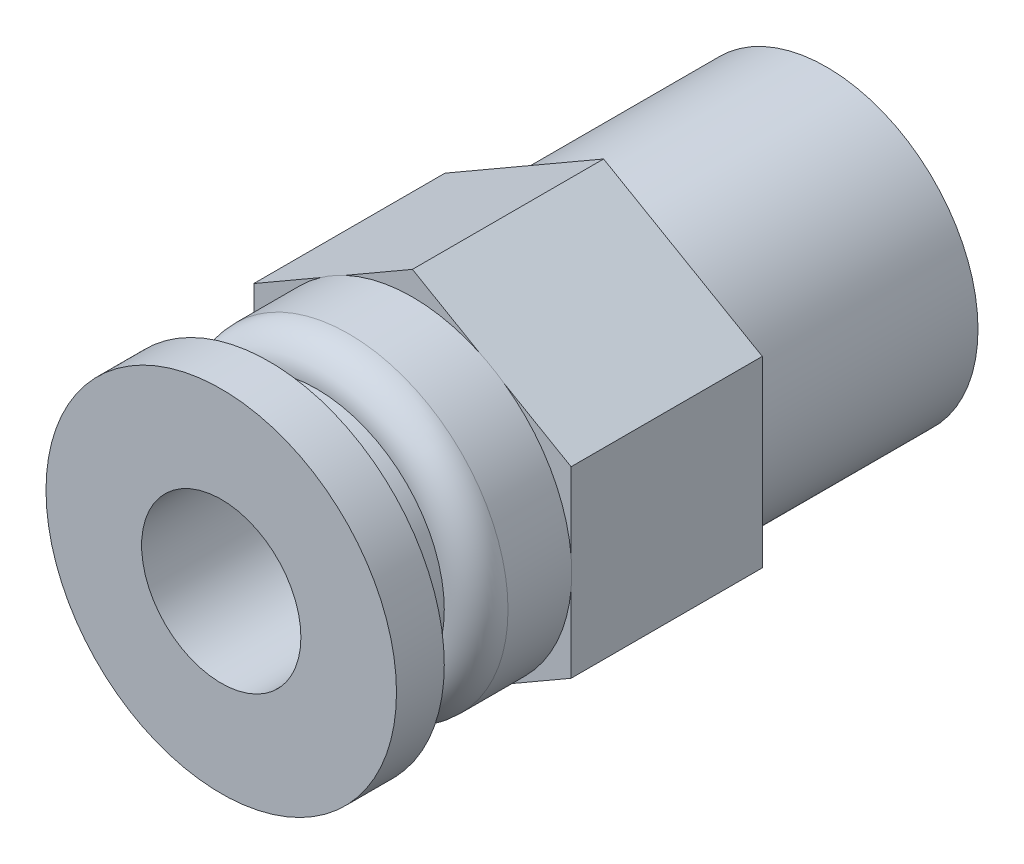
SolidWorks part; units mm, degrees
ref_plane "Front Plane" through (0, 0, 0) normal (0, 0, 1) x (1, 0, 0)
ref_plane "Top Plane" through (0, 0, 0) normal (0, 1, 0) x (1, 0, 0)
ref_plane "Right Plane" through (0, 0, 0) normal (1, 0, 0) x (0, 0, -1)
sketch "Sketch1" plane through (0, 0, 0) normal (0, 0, 1) x (1, 0, 0)
  line L1 (0, 1.5) -> (-1.299, 0.75)
  line L2 (-1.299, 0.75) -> (-1.299, -0.75)
  line L3 (-1.299, -0.75) -> (0, -1.5)
  line L4 (0, -1.5) -> (1.299, -0.75)
  line L5 (1.299, -0.75) -> (1.299, 0.75)
  line L6 (1.299, 0.75) -> (0, 1.5)
  circle A0 centre (0, 0) radius 4.75
  circle A1 centre (0, 0) radius 1.5 construction
  dimension "D1" = 9.5
  dimension "D2" = 3
extrude "Boss-Extrude1" add sketch "Sketch1" along normal blind 7
sketch "Sketch2" plane through (0, 0, 7) normal (0, 0, 1) x (1, 0, 0)
  line L1 (0, 5.75) -> (-4.9796, 2.875)
  line L2 (-4.9796, 2.875) -> (-4.9796, -2.875)
  line L3 (-4.9796, -2.875) -> (0, -5.75)
  line L4 (0, -5.75) -> (4.9796, -2.875)
  line L5 (4.9796, -2.875) -> (4.9796, 2.875)
  line L6 (4.9796, 2.875) -> (0, 5.75)
  circle A0 centre (0, 0) radius 5.75 construction
  circle A1 centre (0, 0) radius 2.5
  dimension "D1" = 11.5
  dimension "D2" = 5
extrude "Boss-Extrude2" add sketch "Sketch2" along normal blind 6
sketch "Sketch3" plane through (0, 0, 13) normal (0, 0, 1) x (1, 0, 0)
  circle A0 centre (0, 0) radius 5
  circle A1 centre (0, 0) radius 2.5 construction
  circle A2 centre (0, 0) radius 2.5
  dimension "D1" = 10
extrude "Boss-Extrude3" add sketch "Sketch3" along normal blind 3
sketch "Sketch4" plane through (0, 0, 16) normal (0, 0, 1) x (1, 0, 0)
  circle A0 centre (0, 0) radius 4
  circle A1 centre (0, 0) radius 2.5 construction
  circle A2 centre (0, 0) radius 2.5
  dimension "D1" = 8
extrude "Boss-Extrude4" add sketch "Sketch4" along normal blind 1.5
fillet "Fillet2" radius 1 1 edges at (5, 0, 16)
fillet "Fillet3" radius 1 1 edges at (2.5, 0, 7)
sketch "Sketch5" plane through (0, 0, 17.5) normal (0, 0, 1) x (1, 0, 0)
  circle A0 centre (0, 0) radius 5.5
  circle A1 centre (0, 0) radius 2.5 construction
  circle A2 centre (0, 0) radius 2.5
  dimension "D1" = 11
extrude "Boss-Extrude5" add sketch "Sketch5" along normal blind 1.5
